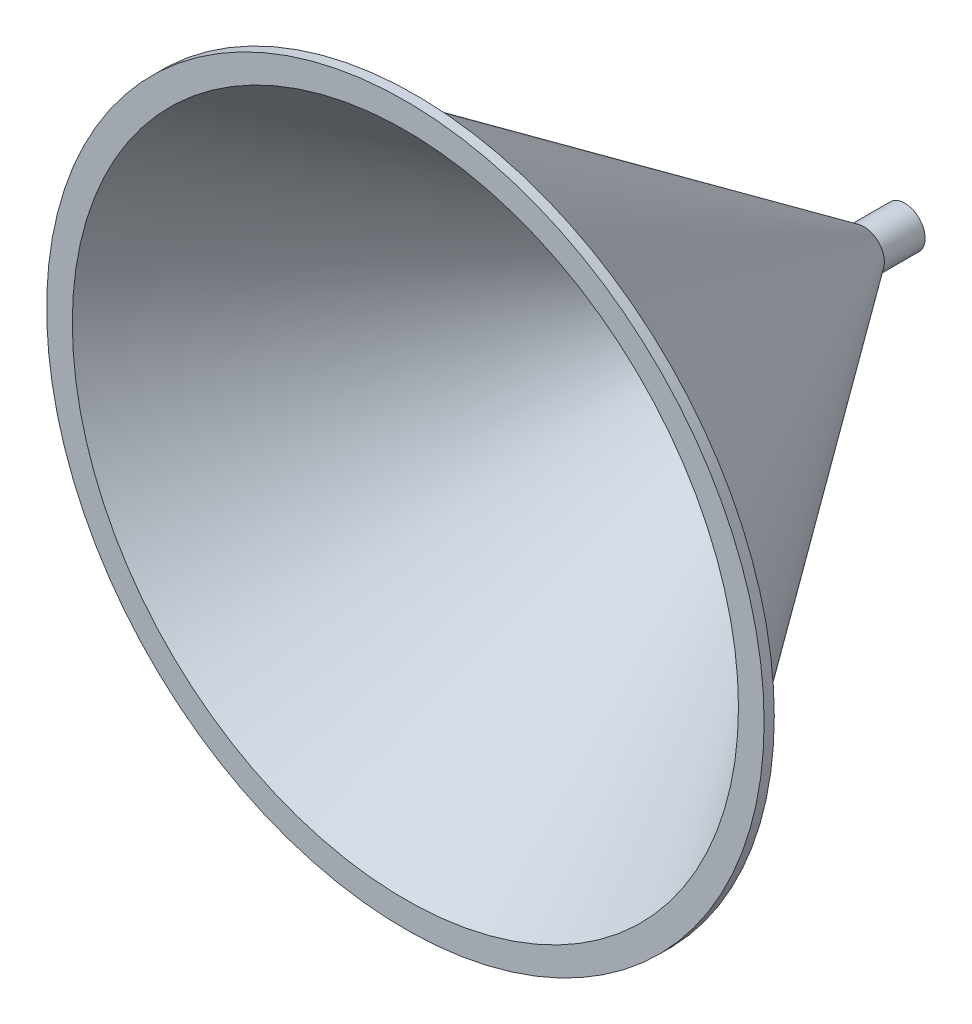
SolidWorks part; units mm, degrees
ref_plane "Alzado" through (0, 0, 0) normal (0, 0, 1) x (1, 0, 0)
ref_plane "Planta" through (0, 0, 0) normal (0, 1, 0) x (1, 0, 0)
ref_plane "Vista lateral" through (0, 0, 0) normal (1, 0, 0) x (0, 0, -1)
sketch "Croquis1" plane through (0, 0, 0) normal (0, 1, 0) x (1, 0, 0)
  line L0 (0, -60) -> (0, 60)
  line L1 (0, 60) -> (-5, 60)
  line L2 (-5, 60) -> (-5, 50)
  line L3 (-5, 50) -> (-83, -60)
  line L4 (-83, -60) -> (-88, -60)
  line L5 (-88, -60) -> (-88, -62.5)
  line L6 (-88, -62.5) -> (0, -62.5)
  line L7 (0, -62.5) -> (0, -60)
  point P4 (0, 0)
  dimension "D1" = 120
  dimension "D2" = 5
  dimension "D3" = 10
  dimension "D4" = 83
  dimension "D5" = 5
  dimension "D6" = 2.5
  dimension "D7" = 88
revolve "Revolución2" add sketch "Croquis1" angle 360 about L0
shell "Vaciado1" thickness 2.5 removed face at (5, 0, -60) removed face at (88, 0, 62.5)
